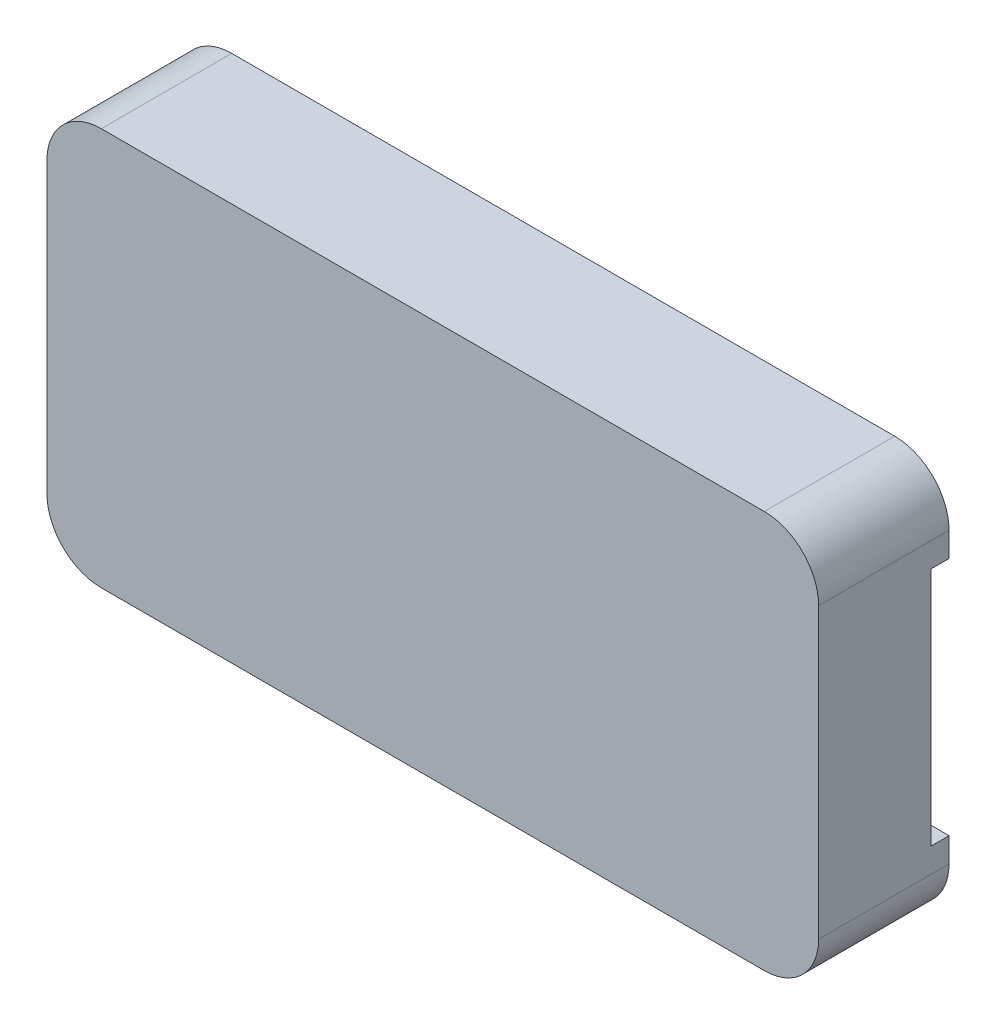
SolidWorks part; units mm, degrees
ref_plane "Plan de face" through (0, 0, 0) normal (0, 0, 1) x (1, 0, 0)
ref_plane "Plan de dessus" through (0, 0, 0) normal (0, 1, 0) x (1, 0, 0)
ref_plane "Plan de droite" through (0, 0, 0) normal (1, 0, 0) x (0, 0, -1)
sketch "Sketch2" plane through (0, 0, 0) normal (0, 0, 1) x (1, 0, 0)
  line L1 (21.3, -10.975) -> (-21.3, -10.975)
  line L2 (21.3, -10.975) -> (21.3, 10.975)
  line L3 (21.3, 10.975) -> (-21.3, 10.975)
  line L4 (-21.3, -10.975) -> (-21.3, 10.975)
  line L5 (21.3, -10.975) -> (-21.3, 10.975) construction
  line L6 (21.3, 10.975) -> (-21.3, -10.975) construction
  point P0 (0, 0)
  dimension "D1" = 42.6
  dimension "D2" = 21.95
extrude "Boss-Extrude1" add sketch "Sketch2" along normal blind 7.2
fillet "Fillet1" radius 3 4 edges at (-21.3, -10.975, 3.6) (21.3, -10.975, 3.6) (21.3, 10.975, 3.6) (-21.3, 10.975, 3.6)
sketch "Sketch3" plane through (0, 0, 0) normal (0, 0, -1) x (-1, 0, 0)
  line L0 (-21.3, 6.625) -> (-17.23, 6.625)
  line L1 (-21.3, -7.975) -> (-21.3, 7.975) construction
  line L2 (-17.23, 6.625) -> (-17.23, -6.625)
  line L3 (-17.23, -6.625) -> (-21.3, -6.625)
  line L4 (21.3, 7.975) -> (21.3, -7.975) construction
  line L5 (-18.3, 10.975) -> (18.3, 10.975) construction
  line L6 (18.3, -10.975) -> (-18.3, -10.975) construction
  line L7 (-21.3, 6.625) -> (-21.3, -6.625)
  dimension "D1" = 38.53
  dimension "D2" = 4.35
  dimension "D3" = 4.35
extrude "Cut-Extrude1" cut sketch "Sketch3" against normal blind 5.2
sketch "Sketch4" plane through (0, 0, 5.2) normal (0, 0, -1) x (-1, 0, 0)
  line L0 (-20.15, 4.925) -> (-20.15, -4.925)
  line L1 (-20.15, -4.925) -> (-18.4, -4.925)
  line L2 (-18.4, -4.925) -> (-18.4, -3.815)
  line L3 (-18.4, -3.815) -> (-19.11, -3.815)
  line L4 (-19.11, -3.815) -> (-19.11, -0.555)
  line L5 (-19.11, -0.555) -> (-18.4, -0.555)
  line L6 (-18.4, -0.555) -> (-18.4, 0.555)
  line L7 (-18.4, 0.555) -> (-19.11, 0.555)
  line L8 (-19.11, 0.555) -> (-19.11, 3.815)
  line L9 (-19.11, 3.815) -> (-18.4, 3.815)
  line L10 (-18.4, 3.815) -> (-18.4, 4.925)
  line L11 (-18.4, 4.925) -> (-20.15, 4.925)
  line L12 (21.3, 7.975) -> (21.3, -7.975) construction
  line L13 (-21.3, 6.625) -> (-21.3, -6.625) construction
  line L15 (18.3, -10.975) -> (-18.3, -10.975) construction
  point P16 (-20.15, 0)
  point P20 (-19.11, 2.1008)
  point P21 (-18.4, 2.9602)
  dimension "D1" = 41.45
  dimension "D2" = 2.9
  dimension "D3" = 15.9
  dimension "D4" = 1.04
  dimension "D5" = 1.11
extrude "Boss-Extrude2" add sketch "Sketch4" along normal blind 5.2
sketch "Sketch5" plane through (0, 0, 5.2) normal (0, 0, -1) x (-1, 0, 0)
  line L3 (-21.3, 6.625) -> (-21.3, -6.625)
  line L7 (-21.3, 6.625) -> (-19.9, 6.625)
  line L8 (-17.23, 6.625) -> (-21.3, 6.625) construction
  line L9 (-19.9, 6.625) -> (-19.9, 4.925)
  line L10 (-18.4, 4.925) -> (-20.15, 4.925) construction
  line L11 (-19.9, 4.925) -> (-20.15, 4.925)
  line L12 (-20.15, 4.925) -> (-20.15, -4.925)
  line L13 (-20.15, -4.925) -> (-19.9, -4.925)
  line L14 (-20.15, -4.925) -> (-18.4, -4.925) construction
  line L15 (-19.9, -4.925) -> (-19.9, -6.625)
  line L16 (-21.3, -6.625) -> (-17.23, -6.625) construction
  line L17 (-19.9, -6.625) -> (-21.3, -6.625)
  dimension "D1" = 0.25
  dimension "D2" = 0.25
extrude "Boss-Extrude3" add sketch "Sketch5" along normal blind 4.2
